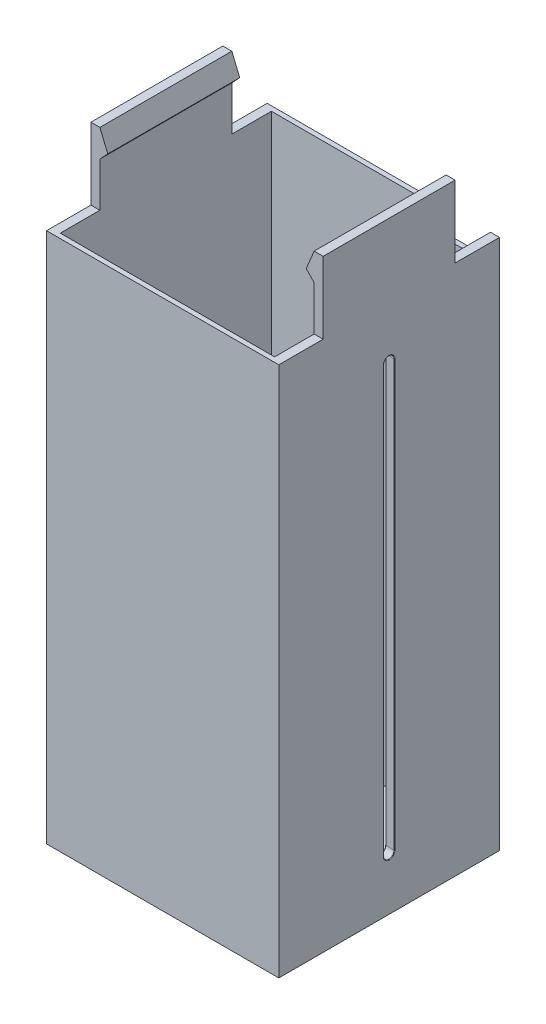
SolidWorks part; units mm, degrees
ref_plane "Front Plane" through (0, 0, 0) normal (0, 0, 1) x (1, 0, 0)
ref_plane "Top Plane" through (0, 0, 0) normal (0, 1, 0) x (1, 0, 0)
ref_plane "Right Plane" through (0, 0, 0) normal (1, 0, 0) x (0, 0, -1)
sketch "Sketch1" plane through (0, 0, 0) normal (0, 1, 0) x (1, 0, 0)
  line L0 (-22, 20.9) -> (42.3707, 20.9) construction
  line L1 (-22, 20.9) -> (22, 20.9)
  line L2 (-22, 20.9) -> (-22, -20.9)
  line L3 (-22, -20.9) -> (22, -20.9)
  line L4 (22, 20.9) -> (22, -20.9)
  line L5 (-22, 20.9) -> (22, -20.9) construction
  line L6 (-22, -20.9) -> (22, 20.9) construction
  line L7 (20.3, 20) -> (-20.3, 20)
  line L8 (20.3, 20) -> (20.3, -20)
  line L9 (20.3, -20) -> (-20.3, -20)
  line L10 (-20.3, 20) -> (-20.3, -20)
  line L11 (20.3, 20) -> (-20.3, -20) construction
  line L12 (20.3, -20) -> (-20.3, 20) construction
  point P0 (0, 0)
  point P6 (0, 0)
  dimension "D1" = 40.6
  dimension "D2" = 40
  dimension "D3" = 1.7
  dimension "D5" = 0.9
extrude "Boss-Extrude1" add sketch "Sketch1" along normal blind 100
sketch "Sketch2" plane through (0, 100, 0) normal (0, 1, 0) x (1, 0, 0)
  line L0 (-23.425, 0) -> (23.575, 0) construction
  line L1 (-22, 20.9) -> (-22, -20.9) construction
  line L3 (-20.3, 24.7662) -> (-20.3, -22.0296) construction
  line L4 (0, 23.9453) -> (0, -27.2839) construction
  line L5 (20.3, 12.5) -> (22, 12.5)
  line L6 (-20.3, -12.5) -> (-22, -12.5)
  line L7 (-20.3, -12.5) -> (-20.3, 12.5)
  line L8 (-20.3, 12.5) -> (-22, 12.5)
  line L9 (-22, -12.5) -> (-22, 12.5)
  line L10 (-20.3, -12.5) -> (-22, 12.5) construction
  line L11 (-20.3, 12.5) -> (-22, -12.5) construction
  line L12 (22, -12.5) -> (22, 12.5)
  line L13 (20.3, -12.5) -> (22, -12.5)
  line L14 (20.3, -12.5) -> (20.3, 12.5)
  line L15 (-20.3, 20) -> (-20.3, -20) construction
  point P11 (-21.15, 0)
  dimension "D2" = 25
  dimension "D3" = 20
extrude "Boss-Extrude2" add sketch "Sketch2" along normal blind 13.6
sketch "Sketch5" plane through (0, 0, 12.5) normal (0, 0, 1) x (1, 0, 0)
  line L0 (-18.8, 110) -> (18.8, 110) construction
  line L1 (20.3, 113.6) -> (20.3, 100) construction
  line L4 (-18.8, 110) -> (-20.3, 108.4)
  line L5 (-20.3, 108.4) -> (-20.3, 113.6)
  line L7 (-20.3, 113.6) -> (-18.8, 110)
  line L8 (20.3, 108.4) -> (20.3, 113.6)
  line L9 (18.8, 110) -> (20.3, 108.4)
  line L10 (20.3, 113.6) -> (18.8, 110)
  line L11 (-20.3, 113.6) -> (-20.3, 100) construction
  dimension "D1" = 10
  dimension "D2" = 1.6
  dimension "D3" = 1.5
  dimension "D4" = 1.6
  dimension "D5" = 1.5
extrude "Boss-Extrude5" add sketch "Sketch5" against normal up to surface (25 mm away) up to face at (21.15, 106.8, -12.5)
sketch "Sketch6" plane through (0, 0, 0) normal (0, -1, 0) x (1, 0, 0)
  line L0 (-22, 20.9) -> (22, 20.9) construction
  line L1 (22, 20.9) -> (-22, 20.9)
  line L2 (22, 20.9) -> (22, -20.9)
  line L3 (22, -20.9) -> (-22, -20.9)
  line L4 (-22, 20.9) -> (-22, -20.9)
extrude "Boss-Extrude6" add sketch "Sketch6" along normal blind 0.6
sketch "Sketch7" plane through (0, 0, -20.9) normal (0, 0, -1) x (-1, 0, 0)
  line L1 (-20.3, 100) -> (-7, 100)
  line L2 (-20.3, 100) -> (-20.3, 95.6)
  line L3 (-20.3, 95.6) -> (-7, 95.6)
  line L4 (-7, 100) -> (-7, 95.6)
  line L5 (-22, 100) -> (22, 100) construction
  line L6 (-22, 100) -> (-22, -0.6) construction
  dimension "D1" = 1.7
  dimension "D2" = 4.4
  dimension "D3" = 13.3
extrude "Cut-Extrude1" cut sketch "Sketch7" against normal blind 10
sketch "Sketch8" plane through (22, 0, 0) normal (1, 0, 0) x (0, 0, -1)
  line L0 (0, -0.6) -> (0, 113.6) construction
  line L1 (20.9, -0.6) -> (-20.9, -0.6) construction
  line L2 (-12.5, 113.6) -> (12.5, 113.6) construction
  line L3 (0, 9.4) -> (0, 90) construction
  line L4 (-1, 9.4) -> (-1, 90)
  line L5 (1, 9.4) -> (1, 90)
  line L6 (12.5, 100) -> (20.9, 100) construction
  arc A0 (-1, 9.4) -> (1, 9.4) centre (0, 9.4) ccw
  arc A1 (1, 90) -> (-1, 90) centre (0, 90) ccw
  point P8 (0, 49.7)
  dimension "D1" = 2
  dimension "D2" = 10
  dimension "D3" = 10
extrude "Cut-Extrude2" cut sketch "Sketch8" against normal blind 10
fillet "Fillet1" radius 0.1 8 edges at (20.3, 8.4, 0) (20.3, 49.7, -1) (20.3, 91, 0) (22, 91, 0) (22, 49.7, -1) (22, 8.4, 0) (20.3, 49.7, 1) (22, 49.7, 1)
